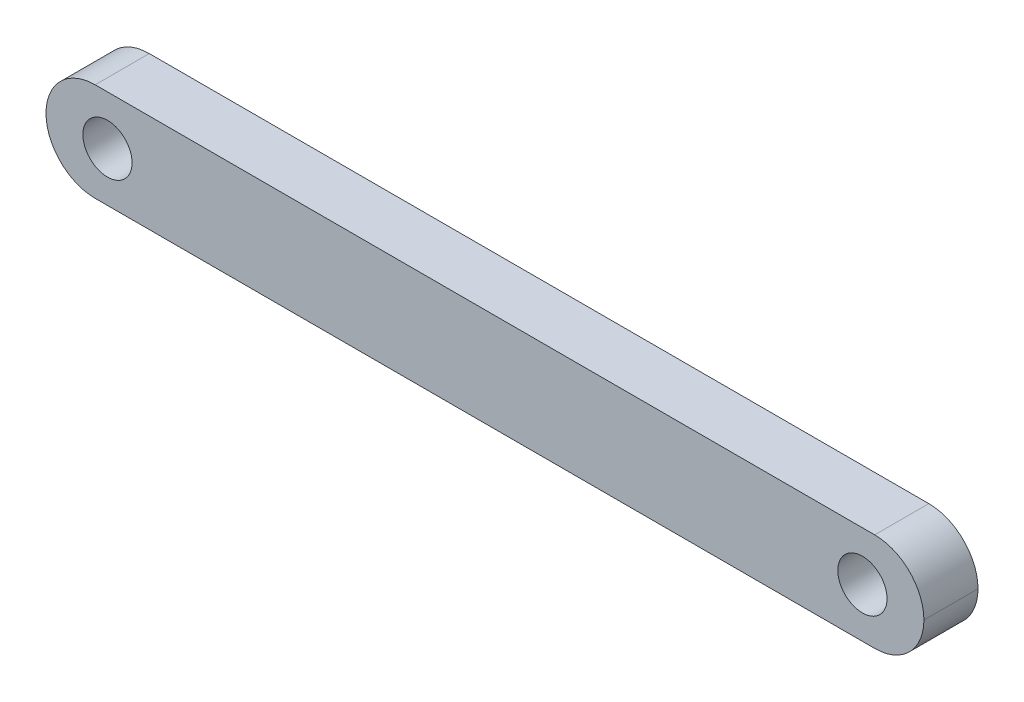
SolidWorks part; units mm, degrees
ref_plane "Alzado" through (0, 0, 0) normal (0, 0, 1) x (1, 0, 0)
ref_plane "Planta" through (0, 0, 0) normal (0, 1, 0) x (1, 0, 0)
ref_plane "Vista lateral" through (0, 0, 0) normal (1, 0, 0) x (0, 0, -1)
sketch "Croquis1" plane through (0, 0, 0) normal (0, 0, 1) x (1, 0, 0)
  line L0 (-62.3478, 12.4167) -> (-62.3478, 8.4167)
  line L1 (-62.3478, 8.4167) -> (-26.6478, 8.4167)
  line L2 (-26.6478, 8.4167) -> (-26.6478, 12.4167)
  line L3 (-26.6478, 12.4167) -> (-62.3478, 12.4167)
  line L4 (-62.3478, 10.4167) -> (-59.8478, 10.4167) construction
  line L5 (-26.6478, 10.4167) -> (-29.1478, 10.4167) construction
  circle A0 centre (-59.8478, 10.4167) radius 1
  circle A1 centre (-29.1478, 10.4167) radius 1
  dimension "D4" = 2
  dimension "D6" = 2
  dimension "D1" = 4
  dimension "D2" = 35.7
  dimension "D3" = 2.5
  dimension "D5" = 2.5
  dimension "D7" = 4
extrude "Saliente-Extruir1" add sketch "Croquis1" along normal blind 2.2
fillet "Redondeo1" radius 2 4 edges at (-62.3478, 8.4167, 1.1) (-62.3478, 12.4167, 1.1) (-26.6478, 8.4167, 1.1) (-26.6478, 12.4167, 1.1)
